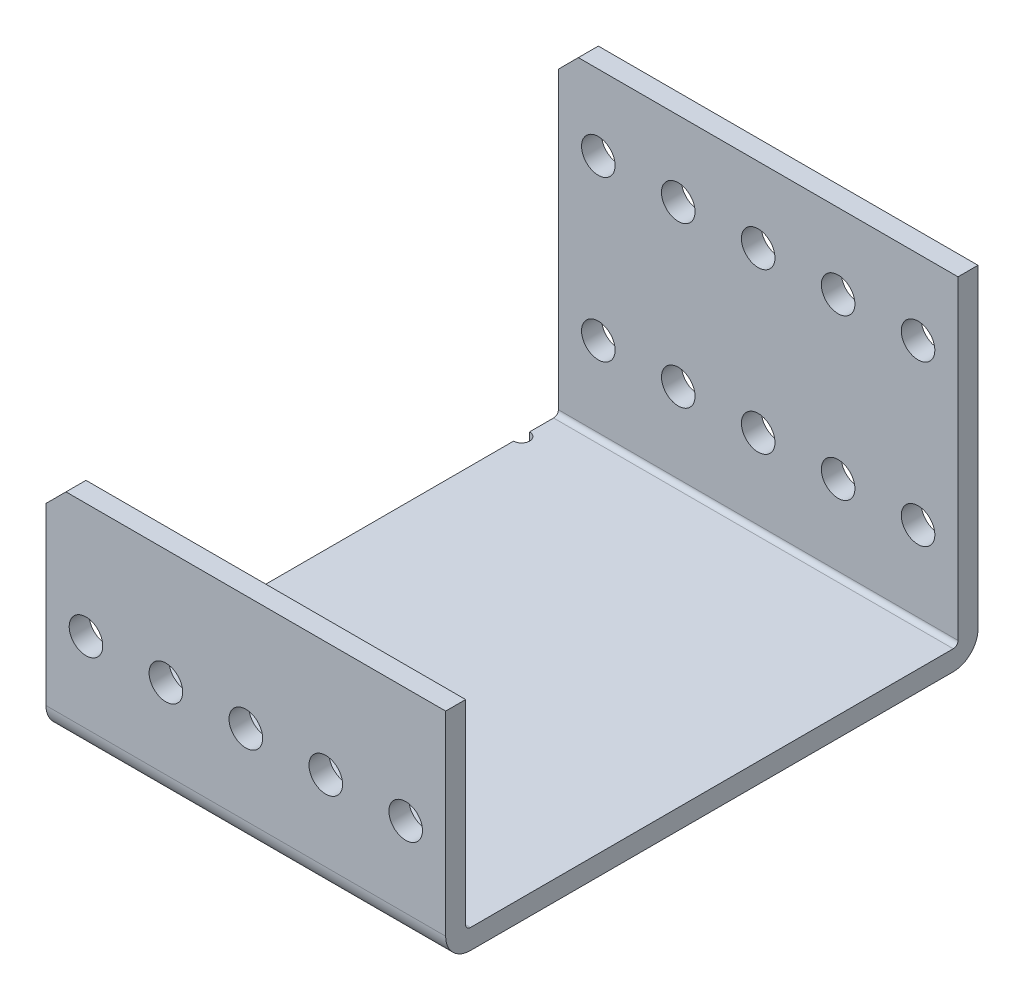
SolidWorks part; units mm, degrees
ref_plane "Front Plane" through (0, 0, 0) normal (0, 0, 1) x (1, 0, 0)
ref_plane "Top Plane" through (0, 0, 0) normal (0, 1, 0) x (1, 0, 0)
ref_plane "Right Plane" through (0, 0, 0) normal (1, 0, 0) x (0, 0, -1)
ref_plane "Plane4" through (0, 57.8164, 0) normal (0, 1, 0) x (1, 0, 0)
sketch "Sketch1" plane through (0, 57.8164, 0) normal (0, 1, 0) x (1, 0, 0)
  line L0 (602.398, -145.5605) -> (602.398, -60.9785)
  line L1 (602.398, -60.9785) -> (-96.102, -60.9785)
  line L2 (-96.102, -60.9785) -> (-96.102, -145.5605)
  line L3 (-96.102, -145.5605) -> (602.398, -145.5605)
  dimension "D1" = 698.5
extrude "Boss-Extrude1" add sketch "Sketch1" against normal blind 34.925
sketch "Sketch2" plane through (602.398, 0, 0) normal (1, 0, 0) x (0, 0, -1)
  line L0 (-60.9785, 57.8164) -> (-142.3855, 57.8164)
  line L1 (-142.3855, 57.8164) -> (-142.3855, 26.0664)
  line L2 (-142.3855, 26.0664) -> (-60.9785, 26.0664)
  line L3 (-60.9785, 26.0664) -> (-60.9785, 57.8164)
extrude "Cut-Extrude1" cut sketch "Sketch2" against normal through all
sketch "Sketch3" plane through (0, 26.0664, 0) normal (0, 1, 0) x (-1, 0, 0)
  line L0 (96.102, 60.9785) -> (-602.398, 60.9785)
  line L1 (-602.398, 60.9785) -> (-602.398, 64.1535)
  line L2 (-602.398, 64.1535) -> (96.102, 64.1535)
  line L3 (96.102, 64.1535) -> (96.102, 60.9785)
  line L5 (-602.398, 142.3855) -> (-602.398, 60.9785) construction
  line L6 (96.102, 142.3855) -> (96.102, 60.9785) construction
extrude "Boss-Extrude2" add sketch "Sketch3" along normal blind 50.8
hole_wizard "M2 Clearance Hole1" positions "Sketch5" profile "Sketch4" hole size "M2" standard "ANSI Metric" end condition through all
sketch "Sketch5" plane through (0, 26.0664, 0) normal (0, 1, 0) x (1, 0, 0)
  point P0 (-96.102, -136.5435)
  point P1 (-96.102, -69.9955)
sketch "Sketch4" plane through (-96.102, 26.0664, 136.5435) normal (1, 0, 0) x (0, 0, 1)
  line L0 (0, 0) -> (0, 3.175)
  line L1 (0, 3.175) -> (1.27, 3.175)
  line L2 (1.27, 3.175) -> (1.27, 0)
  line L5 (1.27, 0) -> (0, 0)
  line L11 (0, -6.35) -> (0, 107.95) construction
  dimension "Thru Hole Dia." = 2.54
  dimension "Thru Hole Depth" = 3.175
hole_wizard "M5 Clearance Hole1" positions "Sketch7" profile "Sketch6" hole size "M5" standard "ANSI Metric" end condition through all
sketch "Sketch7" plane through (0, 0, 60.9785) normal (0, 0, -1) x (-1, 0, 0)
  point P0 (-469.048, 64.9284)
  point P1 (-481.748, 64.9284)
  point P2 (-469.048, 39.5284)
  point P3 (-481.748, 39.5284)
  point P4 (-456.348, 39.5284)
  point P5 (-443.648, 39.5284)
  point P6 (-430.948, 39.5284)
  point P7 (-418.248, 39.5284)
  point P8 (-405.548, 39.5284)
  point P9 (-392.848, 39.5284)
  point P10 (-380.148, 39.5284)
  point P11 (-367.448, 39.5284)
  point P12 (-354.748, 39.5284)
  point P13 (-342.048, 39.5284)
  point P14 (-329.348, 39.5284)
  point P15 (-316.648, 39.5284)
  point P16 (-303.948, 39.5284)
  point P17 (-291.248, 39.5284)
  point P18 (-278.548, 39.5284)
  point P19 (-265.848, 39.5284)
  point P20 (-253.148, 39.5284)
  point P21 (-240.448, 39.5284)
  point P22 (-227.748, 39.5284)
  point P23 (-215.048, 39.5284)
  point P24 (-202.348, 39.5284)
  point P25 (-189.648, 39.5284)
  point P26 (-176.948, 39.5284)
  point P27 (-164.248, 39.5284)
  point P28 (-151.548, 39.5284)
  point P29 (-138.848, 39.5284)
  point P30 (-126.148, 39.5284)
  point P31 (-113.448, 39.5284)
  point P32 (-100.748, 39.5284)
  point P33 (-88.048, 39.5284)
  point P34 (-75.348, 39.5284)
  point P35 (-62.648, 39.5284)
  point P36 (-49.948, 39.5284)
  point P37 (-37.248, 39.5284)
  point P38 (-24.548, 39.5284)
  point P39 (-11.848, 39.5284)
  point P40 (0.852, 39.5284)
  point P41 (13.552, 39.5284)
  point P42 (26.252, 39.5284)
  point P43 (38.952, 39.5284)
  point P44 (51.652, 39.5284)
  point P45 (64.352, 39.5284)
  point P46 (77.052, 39.5284)
  point P47 (89.752, 39.5284)
  point P48 (-456.348, 64.9284)
  point P49 (-443.648, 64.9284)
  point P50 (-430.948, 64.9284)
  point P51 (-418.248, 64.9284)
  point P52 (-405.548, 64.9284)
  point P53 (-392.848, 64.9284)
  point P54 (-380.148, 64.9284)
  point P55 (-367.448, 64.9284)
  point P56 (-354.748, 64.9284)
  point P57 (-342.048, 64.9284)
  point P58 (-329.348, 64.9284)
  point P59 (-316.648, 64.9284)
  point P60 (-303.948, 64.9284)
  point P61 (-291.248, 64.9284)
  point P62 (-278.548, 64.9284)
  point P63 (-265.848, 64.9284)
  point P64 (-253.148, 64.9284)
  point P65 (-240.448, 64.9284)
  point P66 (-227.748, 64.9284)
  point P67 (-215.048, 64.9284)
  point P68 (-202.348, 64.9284)
  point P69 (-189.648, 64.9284)
  point P70 (-176.948, 64.9284)
  point P71 (-164.248, 64.9284)
  point P72 (-151.548, 64.9284)
  point P73 (-138.848, 64.9284)
  point P74 (-126.148, 64.9284)
  point P75 (-113.448, 64.9284)
  point P76 (-100.748, 64.9284)
  point P77 (-88.048, 64.9284)
  point P78 (-75.348, 64.9284)
  point P79 (-62.648, 64.9284)
  point P80 (-49.948, 64.9284)
  point P81 (-37.248, 64.9284)
  point P82 (-24.548, 64.9284)
  point P83 (-11.848, 64.9284)
  point P84 (0.852, 64.9284)
  point P85 (13.552, 64.9284)
  point P86 (26.252, 64.9284)
  point P87 (38.952, 64.9284)
  point P88 (51.652, 64.9284)
  point P89 (64.352, 64.9284)
  point P90 (77.052, 64.9284)
  point P91 (89.752, 64.9284)
  point P97 (-494.448, 64.9284)
  point P98 (-494.448, 39.5284)
  point P99 (-507.148, 64.9284)
  point P100 (-507.148, 39.5284)
  point P101 (-519.848, 64.9284)
  point P102 (-519.848, 39.5284)
  point P103 (-532.548, 64.9284)
  point P104 (-532.548, 39.5284)
  point P105 (-545.248, 64.9284)
  point P106 (-545.248, 39.5284)
  point P107 (-557.948, 64.9284)
  point P108 (-557.948, 39.5284)
  point P109 (-570.648, 64.9284)
  point P110 (-570.648, 39.5284)
  point P111 (-583.348, 64.9284)
  point P112 (-583.348, 39.5284)
  point P113 (-596.048, 64.9284)
  point P114 (-596.048, 39.5284)
  dimension "D1" = 10
sketch "Sketch6" plane through (469.048, 64.9284, 60.9785) normal (1, 0, 0) x (0, 1, 0)
  line L0 (0, 0) -> (0, 84.582)
  line L1 (0, 84.582) -> (2.667, 84.582)
  line L2 (2.667, 84.582) -> (2.667, 0)
  line L5 (2.667, 0) -> (0, 0)
  line L11 (0, -6.35) -> (0, 107.95) construction
  dimension "Thru Hole Dia." = 5.334
  dimension "Thru Hole Depth" = 84.582
chamfer "Chamfer1" distance 3.175 angle 45 4 edges at (602.398, 76.8664, 62.566) (-96.102, 57.8164, 143.973) (602.398, 57.8164, 143.973) (-96.102, 76.8664, 62.566)
fillet "Fillet1" radius 0.762 2 edges at (253.148, 26.0664, 64.1535) (253.148, 26.0664, 142.3855) tangent propagation no
fillet "Fillet2" radius 3.937 2 edges at (253.148, 22.8914, 145.5605) (253.148, 22.8914, 60.9785) tangent propagation no
sketch "Sketch8" plane through (0, 0, 60.9785) normal (0, 0, -1) x (-1, 0, 0)
  line L1 (-693.323, 170.3588) -> (32.602, 170.3588)
  line L2 (-693.323, 170.3588) -> (-693.323, -47.8575)
  line L3 (-693.323, -47.8575) -> (32.602, -47.8575)
  line L4 (32.602, 170.3588) -> (32.602, -47.8575)
  line L5 (-693.323, 170.3588) -> (32.602, -47.8575) construction
  line L6 (-693.323, -47.8575) -> (32.602, 170.3588) construction
  line L7 (38.952, 39.5284) -> (26.252, 39.5284) construction
  point P4 (-330.3605, 61.2506)
  point P5 (32.602, 39.5284)
extrude "Cut-Extrude2" cut sketch "Sketch8" against normal through all
